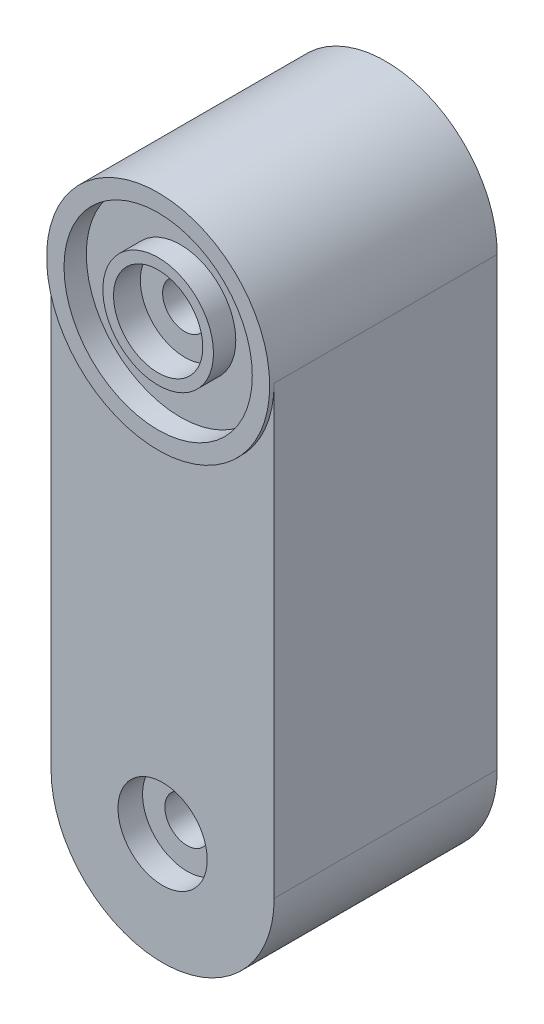
SolidWorks part; units mm, degrees
ref_plane "Ebene vorne" through (0, 0, 0) normal (0, 0, 1) x (1, 0, 0)
ref_plane "Ebene oben" through (0, 0, 0) normal (0, 1, 0) x (1, 0, 0)
ref_plane "Ebene rechts" through (0, 0, 0) normal (1, 0, 0) x (0, 0, -1)
sketch "Skizze4" plane through (0, 0, 0) normal (0, 1, 0) x (1, 0, 0)
  line L1 (-25, -25) -> (25, -25)
  line L2 (-25, -25) -> (-25, 25)
  line L3 (-25, 25) -> (25, 25)
  line L4 (25, -25) -> (25, 25)
  line L5 (-25, -25) -> (25, 25) construction
  line L6 (-25, 25) -> (25, -25) construction
  point P0 (0, 0)
  dimension "D1" = 50
  dimension "D2" = 50
extrude "Aufsatz-Linear austragen1" add sketch "Skizze4" along normal blind 150
sketch "Skizze5" plane through (0, 0, 25) normal (0, 0, 1) x (1, 0, 0)
  line L0 (25, 150) -> (25, 0) construction
  line L1 (-25, 150) -> (25, 150)
  line L2 (-25, 150) -> (-25, 100)
  line L3 (-25, 100) -> (25, 100)
  line L4 (25, 150) -> (25, 100)
  dimension "D1" = 50
extrude "Aufsatz-Linear austragen2" add sketch "Skizze5" along normal blind 1
sketch "Skizze6" plane through (0, 0, 26) normal (0, 0, 1) x (1, 0, 0)
  line L0 (-25, 150) -> (25, 100) construction
  line L1 (25, 100) -> (25, 150) construction
  line L2 (25, 100) -> (25, 150) construction
  line L3 (25, 150) -> (-25, 100) construction
  circle A0 centre (0, 125) radius 5
extrude "Schnitt-Linear austragen1" cut sketch "Skizze6" against normal blind 75
sketch "Skizze8" plane through (0, 0, 25) normal (0, 0, 1) x (1, 0, 0)
  line L0 (-25, 25) -> (-25, 0)
  line L1 (-25, 0) -> (25, 0)
  line L2 (25, 0) -> (25, 25)
  arc A0 (-25, 25) -> (25, 25) centre (0, 25) ccw
  circle A1 centre (0, 25) radius 5
  line M4 (-25, 100) -> (-25, 0)
  line M5 (-25, 0) -> (25, 0)
  line M6 (25, 0) -> (25, 100)
extrude "Schnitt-Linear austragen2" cut sketch "Skizze8" against normal blind 50 contours A0 M4 M5 | A0 L1 M6 | A1 region at (-19.4158, 5.5842, 25) region at (19.4158, 5.5842, 25) region at (0, 25, 25)
sketch "Skizze9" plane through (0, 0, 26) normal (0, 0, 1) x (1, 0, 0)
  line L0 (-25, 150) -> (-25, 100)
  line L1 (-25, 100) -> (25, 100) construction
  line L2 (-25, 150) -> (-25, 100) construction
  line L3 (-25, 100) -> (25, 100)
  line L4 (25, 100) -> (25, 150)
  line L5 (25, 150) -> (-25, 150)
  circle A0 centre (0, 125) radius 25
  line M3 (-25, 150) -> (-25, 100)
  line M6 (25, 150) -> (-25, 150)
extrude "Schnitt-Linear austragen3" cut sketch "Skizze9" against normal up to surface (51 mm away) contours A0 L5 M3 | A0 L4 M6 region at (-19.4158, 144.4158, 26) region at (19.4158, 144.4158, 26) up to face at (5, 25, -25)
sketch "Skizze10" plane through (0, 0, 26) normal (0, 0, 1) x (1, 0, 0)
  line L0 (-25, 125) -> (-25, 100)
  line L1 (-25, 100) -> (25, 100)
  line L2 (25, 100) -> (25, 125)
  circle A0 centre (0, 125) radius 25
  line M2 (25, 100) -> (25, 125)
  line M4 (-25, 125) -> (-25, 100)
  line M5 (-25, 100) -> (25, 100)
extrude "Schnitt-Linear austragen4" cut sketch "Skizze10" against normal up to surface (1 mm away) contours A0 M4 M5 | A0 L1 M2 region at (-19.4158, 105.5842, 26) region at (19.4158, 105.5842, 26) up to face at (5, 25, 25)
sketch "Skizze11" plane through (0, 0, 26) normal (0, 0, 1) x (1, 0, 0)
  circle A0 centre (0, 125) radius 21.1
  circle A1 centre (0, 125) radius 12.4
  dimension "D1" = 24.8
  dimension "D2" = 42.2
extrude "Schnitt-Linear austragen5" cut sketch "Skizze11" against normal blind 5 contours A0 | A1
sketch "Skizze12" plane through (0, 0, -25) normal (0, 0, -1) x (-1, 0, 0)
  circle A0 centre (0, 125) radius 10.2
  circle A1 centre (0, 25) radius 10
extrude "Schnitt-Linear austragen6" cut sketch "Skizze12" against normal blind 5.5
sketch "Skizze13" plane through (0, 0, 26) normal (0, 0, 1) x (1, 0, 0)
  circle A1 centre (0, 125) radius 10
extrude "Schnitt-Linear austragen7" cut sketch "Skizze13" against normal blind 6 contours A1
sketch "Skizze14" plane through (0, 0, 25) normal (0, 0, 1) x (1, 0, 0)
  circle A0 centre (0, 25) radius 10
extrude "Schnitt-Linear austragen8" cut sketch "Skizze14" against normal blind 5.5
